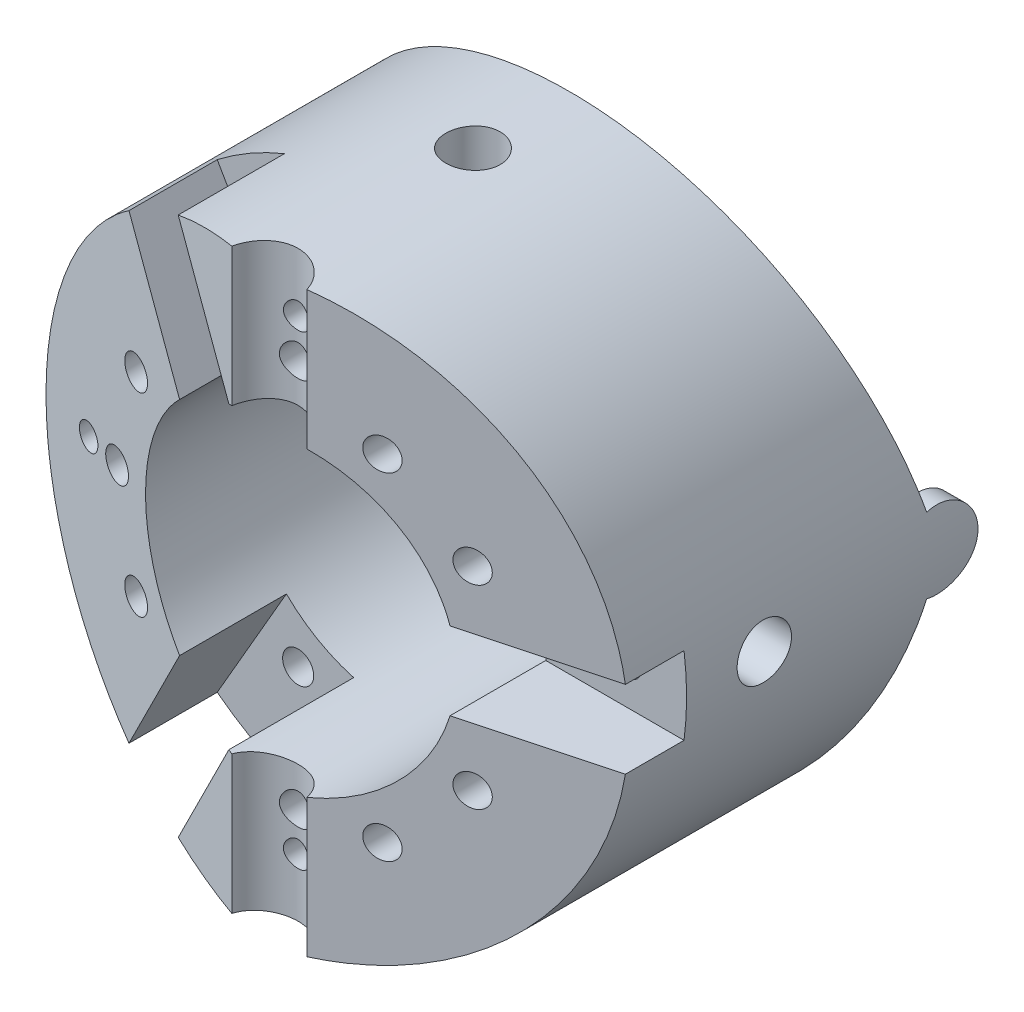
SolidWorks part; units mm, degrees
ref_plane "前视基准面" through (0, 0, 0) normal (0, 0, 1) x (1, 0, 0)
ref_plane "上视基准面" through (0, 0, 0) normal (0, 1, 0) x (1, 0, 0)
ref_plane "右视基准面" through (0, 0, 0) normal (1, 0, 0) x (0, 0, -1)
sketch "草图1" plane through (0, 0, 0) normal (0, 0, 1) x (1, 0, 0)
  circle A0 centre (0, 0) radius 7.5
  dimension "D1" = 15
extrude "凸台-拉伸1" add sketch "草图1" along normal blind 10
sketch "草图2" plane through (0, 0, 0) normal (1, 0, 0) x (0, 0, -1)
  line L0 (0, 0) -> (-2.0096, 7.5)
  line L1 (0, 7.5) -> (-10, 7.5) construction
  line L2 (-2.0096, 7.5) -> (0, 7.5)
  line L3 (0, 7.5) -> (0, 0)
  line L4 (0, 0) -> (-2.0096, -7.5)
  line L5 (-10, -7.5) -> (0, -7.5) construction
  line L6 (-2.0096, -7.5) -> (0, -7.5)
  line L7 (0, -7.5) -> (0, 0)
  dimension "D1" = 15
  dimension "D2" = 15
extrude "切除-拉伸1" cut sketch "草图2" against normal through all and the other way through all contours L3 L2 L0 | L6 L7 L4 region at (0, 5, 0.6699) region at (0, -5, 0.6699)
sketch "草图3" plane through (0, 0, 0) normal (0, 1, 0) x (1, 0, 0)
  line L0 (0, 0) -> (0, -10) construction
  line L1 (-7.5, -10) -> (7.5, -10) construction
  line L2 (0, -10) -> (7.5, -10)
  line L3 (7.5, -10) -> (7.5, -7.9904)
  line L4 (7.5, -7.9904) -> (0, -10)
  line L5 (0, -10) -> (-7.5, -7.9904)
  line L6 (-7.5, 0) -> (-7.5, -10) construction
  line L7 (-7.5, -7.9904) -> (-7.5, -10)
  line L8 (-7.5, -10) -> (0, -10)
  dimension "D1" = 15
  dimension "D2" = 15
extrude "切除-拉伸2" cut sketch "草图3" against normal through all and the other way through all contours L3 L4 L2 | L7 L8 L5 region at (5, 0, 9.3301) region at (-5, 0, 9.3301)
sketch "草图6" plane through (0, 0, 0) normal (1, 0, 0) x (0, 0, -1)
  circle A0 centre (0, 0) radius 1
  dimension "D1" = 2
extrude "凸台-拉伸2" add sketch "草图6" against normal up to surface and the other way up to surface up to face at (0, 0, 7.9904) other way up to face at (0, 0, 7.9904)
sketch "草图7" plane through (0, 0, 0) normal (0, 1, 0) x (1, 0, 0)
  circle A0 centre (0, -10) radius 1
  dimension "D1" = 2
extrude "切除-拉伸7" cut sketch "草图7" against normal through all and the other way through all
sketch "草图8" plane through (0, 0, 0) normal (0, 0, 1) x (1, 0, 0)
  circle A0 centre (0, 0) radius 4
  dimension "D1" = 8
extrude "切除-拉伸9" cut sketch "草图8" against normal through all and the other way through all
sketch "草图9" plane through (0, 0, 0) normal (0, 0, 1) x (1, 0, 0)
  line L0 (0, 0) -> (-5, 0) construction
  circle A0 centre (0, 0) radius 5 construction
  circle A1 centre (-5, 0) radius 0.4
  circle A2 centre (-4.3301, 2.5) radius 0.4
  circle A3 centre (-2.5, 4.3301) radius 0.4
  circle A4 centre (0, 5) radius 0.4
  circle A5 centre (2.5, 4.3301) radius 0.4
  circle A6 centre (4.3301, 2.5) radius 0.4
  circle A7 centre (5, 0) radius 0.4
  circle A8 centre (4.3301, -2.5) radius 0.4
  circle A9 centre (2.5, -4.3301) radius 0.4
  circle A10 centre (0, -5) radius 0.4
  circle A11 centre (-2.5, -4.3301) radius 0.4
  circle A12 centre (-4.3301, -2.5) radius 0.4
  point P29 (0, 0)
  dimension "D1" = 10
  dimension "D2" = 0.8
  dimension "D3" = 12
extrude "切除-拉伸10" cut sketch "草图9" against normal through all and the other way through all
sketch "草图10" plane through (0, 0, 0) normal (0, 0, 1) x (1, 0, 0)
  line L0 (0, 0) -> (-6, 0) construction
  circle A0 centre (0, 0) radius 6 construction
  circle A1 centre (-6, 0) radius 0.325
  circle A2 centre (0, 6) radius 0.325
  circle A3 centre (6, 0) radius 0.325
  circle A4 centre (0, -6) radius 0.325
  point P14 (0, 0)
  dimension "D1" = 12
  dimension "D2" = 0.65
  dimension "D3" = 4
extrude "切除-拉伸11" cut sketch "草图10" against normal through all and the other way through all
ref_plane "基准面1" through (0, 0, -1) normal (0, 0, -1) x (-1, 0, 0)
sketch "草图11" plane through (0, 0, -1) normal (0, 0, -1) x (-1, 0, 0)
  line L0 (-5.6596, -0.9659) -> (-5.6596, 0.9659) construction
  line L1 (-3.8816, -0.9659) -> (-7.4375, -0.9659) construction
  line L2 (-7.433, -1) -> (-3.873, -1) construction
  line L3 (-4.4096, -1) -> (-6.9096, -1)
  line L4 (-4.4096, -1) -> (-4.4096, 1)
  line L5 (-4.4096, 1) -> (-6.9096, 1)
  line L6 (-6.9096, -1) -> (-6.9096, 1)
  line L7 (-4.4096, -1) -> (-6.9096, 1) construction
  line L8 (-4.4096, 1) -> (-6.9096, -1) construction
  line L9 (-3.873, 1) -> (-7.433, 1) construction
  line L10 (0, 0) -> (0, 7.5) construction
  line L11 (4.4096, -1) -> (6.9096, -1)
  line L12 (6.9096, -1) -> (6.9096, 1)
  line L13 (4.4096, 1) -> (6.9096, 1)
  line L14 (4.4096, -1) -> (4.4096, 1)
  arc A0 (7.4375, 0.9659) -> (-7.4375, 0.9659) centre (0, 0) ccw construction
  point P4 (-5.6596, 0)
  dimension "D1" = 2.5
extrude "切除-拉伸12" cut sketch "草图11" against normal blind 1
ref_plane "基准面2" through (0, -7.5, 0) normal (0, -1, 0) x (-1, 0, 0)
sketch "草图12" plane through (0, -7.5, 0) normal (0, -1, 0) x (-1, 0, 0)
  line L0 (0, -9) -> (0, -2.0096) construction
  arc A0 (0.9659, -9.7412) -> (-0.9659, -9.7412) centre (0, -10) ccw construction
  circle A1 centre (0, -4.5) radius 0.7
  ellipse E0 centre (0, 0) end of major axis (-7.5, 0) minor radius 2.0096 (-7.4375, -0.2588) -> (7.4375, -0.2588) ccw construction
  dimension "D1" = 1.4
  dimension "D2" = 4.5
extrude "切除-拉伸13" cut sketch "草图12" against normal blind 1.5
pattern_circular "阵列(圆周)1" count 4 over 360 about axis through (0, 0, 10) along (0, 0, -1) of "切除-拉伸13"
ref_plane "基准面3" through (0, 0, 10) normal (0, 0, 1) x (1, 0, 0)
sketch "草图15" plane through (0, 0, 10) normal (0, 0, 1) x (1, 0, 0)
  line L0 (0, 0) -> (7.5, 0) construction
  line L2 (0.7856, 1) -> (8.0925, 1)
  line L3 (0.7856, 1) -> (0.7856, -1)
  line L4 (0.7856, -1) -> (8.0925, -1)
  line L5 (8.0925, 1) -> (8.0925, -1)
  line L6 (0.7856, 1) -> (8.0925, -1) construction
  line L7 (0.7856, -1) -> (8.0925, 1) construction
  arc A0 (0.9659, -7.4375) -> (0.9659, 7.4375) centre (0, 0) ccw construction
  point P6 (4.439, 0)
  dimension "D1" = 2
extrude "切除-拉伸14" cut sketch "草图15" against normal blind 3.5
pattern_circular "阵列(圆周)2" count 3 over 360 about axis through (0, 0, 10) along (0, 0, -1) of "切除-拉伸14"
